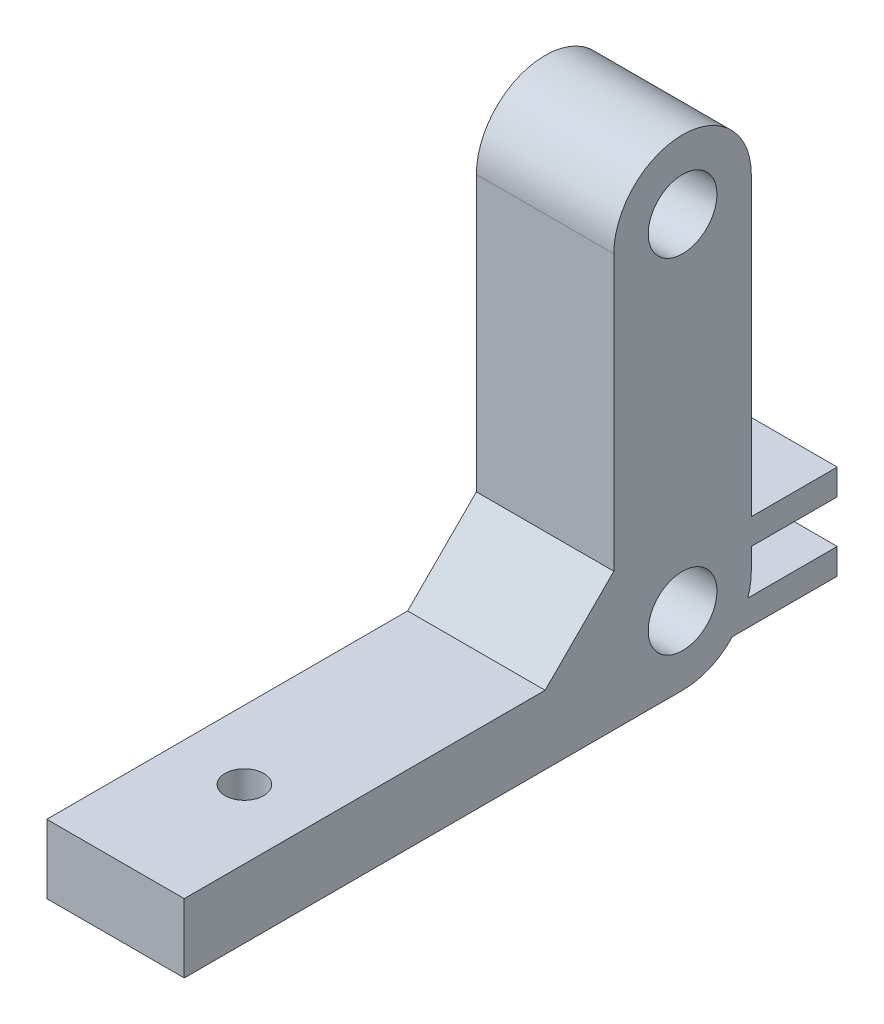
SolidWorks part; units mm, degrees
material "ABS"
ref_plane "Front Plane" through (0, 0, 0) normal (0, 0, 1) x (1, 0, 0)
ref_plane "Top Plane" through (0, 0, 0) normal (0, 1, 0) x (1, 0, 0)
ref_plane "Right Plane" through (0, 0, 0) normal (1, 0, 0) x (0, 0, -1)
sketch "Sketch1" plane through (0, 0, 0) normal (1, 0, 0) x (0, 0, -1)
  line L0 (-10.3091, -58.7899) -> (-58.9824, -58.7899)
  line L1 (7.0176, -45.2899) -> (17.0176, -45.2899)
  line L2 (-8.9824, -10.7899) -> (-8.9824, -42.7899)
  line L3 (-10.3091, -58.7899) -> (-0.9824, -58.7899)
  line L4 (7.0176, -10.7899) -> (7.0176, -45.2899)
  line L5 (-58.9824, -58.7899) -> (-58.9824, -50.7899)
  line L6 (-58.9824, -50.7899) -> (-16.9824, -50.7899)
  line L7 (-8.9824, -42.7899) -> (-16.9824, -50.7899)
  line L8 (17.0176, -45.2899) -> (17.0176, -48.2899)
  line L9 (17.0176, -48.2899) -> (7.0176, -48.2899)
  line L10 (4.8271, -56.2899) -> (17.0176, -56.2899)
  line L11 (17.0176, -56.2899) -> (17.0176, -53.2899)
  line L12 (17.0176, -53.2899) -> (6.617, -53.2899)
  line L13 (7.0176, -48.2899) -> (7.0176, -50.7899)
  circle A0 centre (-0.9824, -10.7899) radius 4
  circle A1 centre (-0.9824, -50.7899) radius 4
  arc A2 (-8.9824, -10.7899) -> (7.0176, -10.7899) centre (-0.9824, -10.7899) cw
  arc A3 (-0.9824, -58.7899) -> (4.8271, -56.2899) centre (-0.9824, -50.7899) ccw
  arc A4 (6.617, -53.2899) -> (7.0176, -50.7899) centre (-0.9824, -50.7899) ccw
  point P8 (-8.9824, -50.7899)
  dimension "D1" = 8
  dimension "D2" = 8
  dimension "D4" = 8
  dimension "D11" = 8
  dimension "D3" = 40
  dimension "D5" = 8
  dimension "D6" = 8
  dimension "D7" = 8
  dimension "D8" = 8
  dimension "D9" = 50
  dimension "D10" = 8
  dimension "D12" = 3
  dimension "D14" = 3
  dimension "D15" = 5
  dimension "D16" = 2.5
  dimension "D17" = 10
extrude "Boss-Extrude1" add sketch "Sketch1" against normal blind 16
sketch "Sketch2" plane through (0, -50.7899, 0) normal (0, 1, 0) x (1, 0, 0)
  line L0 (-16, -58.9824) -> (0, -58.9824) construction
  line L1 (0, -16.9824) -> (0, -58.9824) construction
  circle A0 centre (-8, -43.9824) radius 2.25
  dimension "D1" = 4.5
  dimension "D2" = 15
  dimension "D3" = 8
extrude "Cut-Extrude1" cut sketch "Sketch2" against normal through all
ref_point "Point1"
sketch "Sketch3" plane through (0, -45.2899, 0) normal (0, 1, 0) x (1, 0, 0)
  line L0 (-16, 17.0176) -> (0, 17.0176) construction
  line L1 (0, 17.0176) -> (0, 7.0176) construction
  circle A0 centre (-8, 12.0176) radius 1.75
  dimension "D1" = 3.5
  dimension "D2" = 5
  dimension "D3" = 8
extrude "Cut-Extrude2" cut sketch "Sketch3" against normal through all
ref_axis "Z Axis" through (-16.8, 0, 0) along (1, 0, 0)
ref_axis "Y Axis" through (0, 0.0101, 0) along (0, -1, 0)
ref_axis "X Axis" through (0, 0, -20.8176) along (0, 0, 1)
equation "\"rod_diameter\"= 8"
equation "\"D1@Sketch1\"=\"rod_diameter\""
equation "\"D2@Sketch1\"=\"rod_diameter\""
equation "\"D5@Sketch1\"  = \"rod_radius\" + \"rod_hole_thickness\""
equation "\"D6@Sketch1\"  = \"rod_radius\" + \"rod_hole_thickness\""
equation "\"D7@Sketch1\"  = \"rod_radius\" + \"rod_hole_thickness\""
equation "\"rod_hole_thickness\"= 4"
equation "\"D8@Sketch1\"  = \"rod_radius\" + \"rod_hole_thickness\""
equation "\"D4@Sketch1\"  = \"rod_radius\" + \"rod_hole_thickness\""
equation "\"D11@Sketch1\" = \"rod_radius\" + \"rod_hole_thickness\""
equation "\"rod_radius\"= \"rod_diameter\" / 2"
equation "\"D1@Boss-Extrude1\"= \"rod_diameter\" + \"rod_hole_thickness\" * 2"
equation "\"D3@Sketch2\"=\"rod_radius\"+\"rod_hole_thickness\""
equation "\"platter_diameter\"= 320"
equation "\"platter_radius\"= \"platter_diameter\" / 2"
equation "\"extruder_mount_hole_spacing\"= 75"
equation "\"arm_rod_spacing\"= 40"
equation "\"D3@Sketch1\"=\"arm_rod_spacing\""
equation "\"D2@Sketch3\" = \"D17@Sketch1\" / 2"
equation "\"D3@Sketch3\"= \"D1@Boss-Extrude1\" / 2"
equation "\"top_frame_spacing\"= 90"
equation "\"motor_level_rod_spacing\"= 15"
equation "\"linear_bearing_diameter\"= 15"
equation "\"z_rod_spacing\"= 75"
equation "\"z_drive_rod_offset\"= 12"
equation "\"platter_rod_spacing\"= 50"
equation "\"rod_nut_thickness\"= 6.5"
equation "\"rod_nut_inscribed_diameter\"= 13"
equation "\"z_height\"= 400"
equation "\"gear_pitch\"=2"
equation "\"r_gear_teeth\"= 450"
equation "\"theta_gear_teeth\"= 385"
equation "\"sheet_thickness\"=5.333"
equation "\"sheet_tab_hole_thickness\"= \"sheet_thickness\""
equation "\"sheet_tab_width\"= \"sheet_thickness\"*2"
equation "\"sheet_double_tab_width\"= 35"
equation "\"sheet_bolt_diameter\"= 3"
equation "\"sheet_bolt_length\"= 16"
equation "\"sheet_nut_diameter\"= 5.5"
equation "\"sheet_nut_thickness\"= 2.5"
equation "\"sheet_nut_depth\"= 10"
equation "\"bearing_outside_diameter\"= 22"
equation "\"bearing_thickness\"= 7"
equation "\"corner_part_thickness\"= \"sheet_thickness\" + \"bearing_thickness\""
equation "\"setscrew_nut_diameter\"= 6"
equation "\"setscrew_nut_thickness\"= 3"
equation "\"setscrew_bolt_diameter\"= 3"
equation "\"motor_shaft_diameter\"= 5.7"
equation "\"printed_hole_tolerance\"= 0.5"
equation "\"D1@Sketch2\"=4.00 +\"printed_hole_tolerance\""
equation "\"D1@Sketch3\"=\"sheet_bolt_diameter\"+\"printed_hole_tolerance\""
